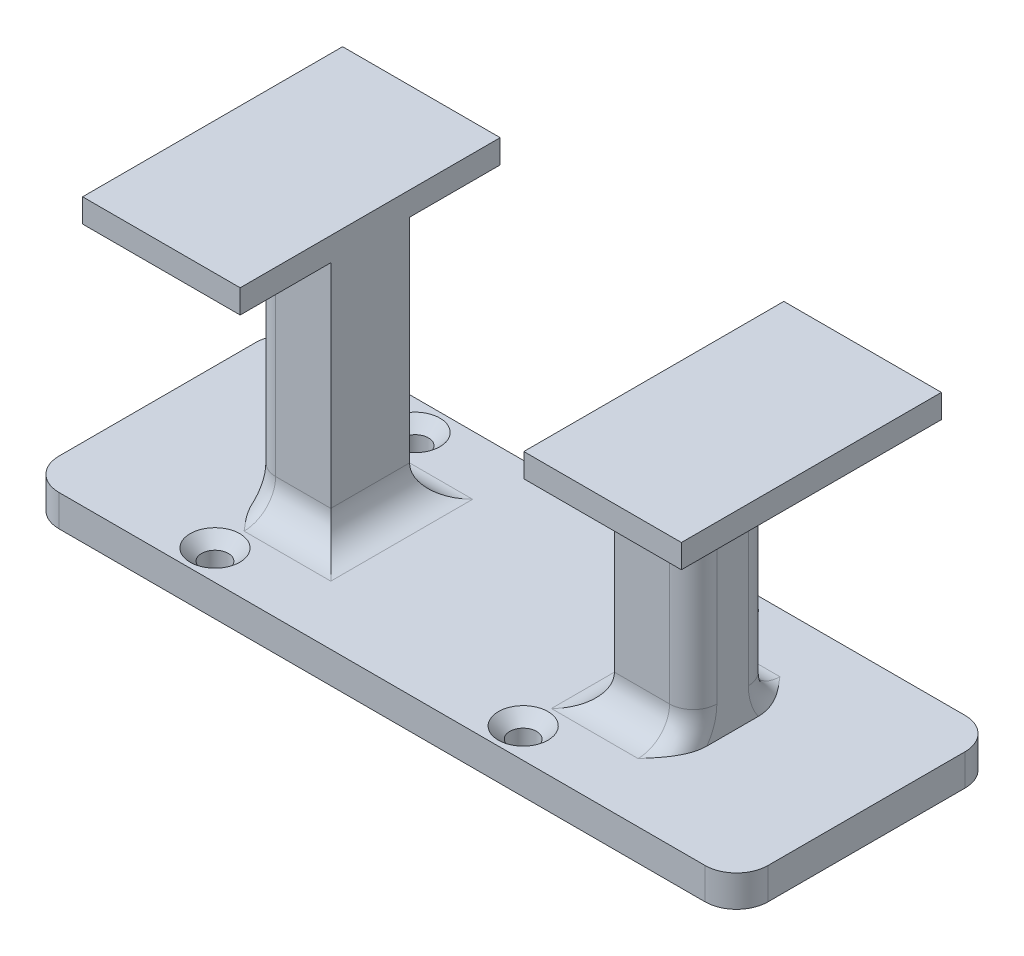
SolidWorks part; units mm, degrees
ref_plane "Plan de face" through (0, 0, 0) normal (0, 0, 1) x (1, 0, 0)
ref_plane "Plan de dessus" through (0, 0, 0) normal (0, 1, 0) x (1, 0, 0)
ref_plane "Plan de droite" through (0, 0, 0) normal (1, 0, 0) x (0, 0, -1)
sketch "Esquisse1" plane through (0, 0, 0) normal (0, 1, 0) x (1, 0, 0)
  line L0 (45, 0) -> (45, 33) construction
  line L1 (0, 0) -> (90, 0)
  line L2 (0, 0) -> (0, 33)
  line L3 (0, 33) -> (90, 33)
  line L4 (90, 0) -> (90, 33)
  line L5 (25.44, 3.8) -> (64.56, 3.8) construction
  line L6 (25.44, 3.8) -> (25.44, 29.2) construction
  line L7 (25.44, 29.2) -> (64.56, 29.2) construction
  line L9 (45, 3.8) -> (45, 29.2) construction
  line L10 (25.44, 16.5) -> (64.56, 16.5) construction
  line L11 (0, 16.5) -> (90, 16.5) construction
  line L12 (64.56, 29.2) -> (64.56, 3.8) construction
  dimension "D1" = 90
  dimension "D2" = 39.12
  dimension "D3" = 33
  dimension "D4" = 25.4
extrude "Boss.-Extru.1" add sketch "Esquisse1" along normal blind 4
sketch "Esquisse2" plane through (0, 4, 0) normal (0, 1, 0) x (1, 0, 0)
  line L1 (20, 29.2) -> (59.12, 29.2) construction
  line L2 (20, 29.2) -> (20, 3.8) construction
  line L3 (20, 3.8) -> (59.12, 3.8) construction
  line L4 (59.12, 29.2) -> (59.12, 3.8) construction
  line L7 (90, 16.5) -> (0, 16.5) construction
  line L8 (90, 0) -> (90, 33) construction
  line L9 (0, 33) -> (0, 0) construction
  line L11 (59.12, 16.5) -> (20, 16.5) construction
  circle A1 centre (20, 29.2) radius 1.5
  circle A2 centre (59.12, 29.2) radius 1.5
  circle A3 centre (59.12, 3.8) radius 1.5
  circle A4 centre (20, 3.8) radius 1.5
  dimension "D3" = 3
  dimension "D4" = 3
  dimension "D5" = 3
  dimension "D6" = 3
  dimension "D1" = 39.12
  dimension "D2" = 25.4
  dimension "D7" = 20
extrude "Enlèv. mat.-Extru.1" cut sketch "Esquisse2" against normal up to surface (4 mm away) up to face at (45, 0, -16.5)
sketch "Esquisse3" plane through (0, 4, 0) normal (0, 1, 0) x (1, 0, 0)
  line L0 (90, 0) -> (90, 33) construction
  line L1 (17, 21.5) -> (27, 21.5)
  line L6 (17, 21.5) -> (17, 11.5)
  line L7 (17, 11.5) -> (27, 11.5)
  line L8 (27, 21.5) -> (27, 11.5)
  line L9 (63, 21.5) -> (73, 21.5)
  line L10 (63, 21.5) -> (63, 11.5)
  line L11 (63, 11.5) -> (73, 11.5)
  line L12 (73, 21.5) -> (73, 11.5)
  line L14 (0, 33) -> (0, 0) construction
  line L15 (0, 16.5) -> (22.5, 16.5) construction
  line L16 (17, 16.5) -> (27, 16.5) construction
  line L17 (73, 16.5) -> (63, 16.5) construction
  dimension "D1" = 10
  dimension "D2" = 10
  dimension "D3" = 10
  dimension "D4" = 10
  dimension "D5" = 17
  dimension "D6" = 17
extrude "Boss.-Extru.2" add sketch "Esquisse3" along normal blind 31
sketch "Esquisse4" plane through (0, 35, 0) normal (0, 1, 0) x (1, 0, 0)
  line L15 (90, 33) -> (0, 33) construction
  line L16 (27, 33) -> (7, 33)
  line L17 (27, 33) -> (27, 0)
  line L18 (27, 0) -> (7, 0)
  line L19 (7, 33) -> (7, 0)
  line L20 (0, 0) -> (90, 0) construction
  line L21 (27, 11.5) -> (27, 21.5) construction
  line L22 (63, 33) -> (83, 33)
  line L23 (63, 33) -> (63, 0)
  line L24 (63, 0) -> (83, 0)
  line L25 (83, 33) -> (83, 0)
  line L26 (63, 21.5) -> (63, 11.5) construction
  dimension "D1" = 20
  dimension "D2" = 20
extrude "Boss.-Extru.3" add sketch "Esquisse4" along normal blind 3
fillet "Congé1" radius 4 10 edges at (22, 4, -21.5) (68, 4, -21.5) (68, 4, -11.5) (22, 4, -11.5) (63, 4, -16.5) (27, 4, -16.5) (90, 2, 0) (90, 2, -33) (0, 2, -33) (0, 2, 0)
hole_wizard "Fraisage pour vis à tête fraisée M31" positions "Esquisse5" profile "Esquisse6" countersink size "M3" standard "ISO"
sketch "Esquisse5" plane through (0, 4, 0) normal (0, 1, 0) x (1, 0, 0)
  point P0 (59.12, 3.8)
  point P3 (59.12, 29.2)
  point P6 (20, 3.8)
  point P9 (20, 29.2)
sketch "Esquisse6" plane through (59.12, 4, -3.8) normal (1, 0, 0) x (0, 0, 1)
  line L0 (0, 0) -> (0, 11.0215)
  line L1 (0, 11.0215) -> (1.7, 10)
  line L2 (1.7, 10) -> (1.7, 1.45)
  line L3 (1.7, 1.45) -> (3.15, 0)
  line L5 (3.15, 0) -> (0, 0)
  line L6 (-1.7, 1.45) -> (-3.15, 0) construction
  line L10 (0, 11.0215) -> (-1.7, 10) construction
  line L11 (0, -6.35) -> (0, 107.95) construction
  dimension "Diamètre du perçage" = 3.4
  dimension "Profondeur du perçage" = 10
  dimension "Diamètre du fraisage entrant" = 6.3
  dimension "Angle du fraisage entrant" = 90
  dimension "Angle de pointe" = 118
fillet "Congé2" radius 3 8 edges at (73, 21.5, -21.5) (73, 21.5, -11.5) (17, 21.5, -11.5) (17, 21.5, -21.5) (73, 5.1716, -22.6716) (73, 5.1716, -10.3284) (17, 5.1716, -10.3284) (17, 5.1716, -22.6716)
